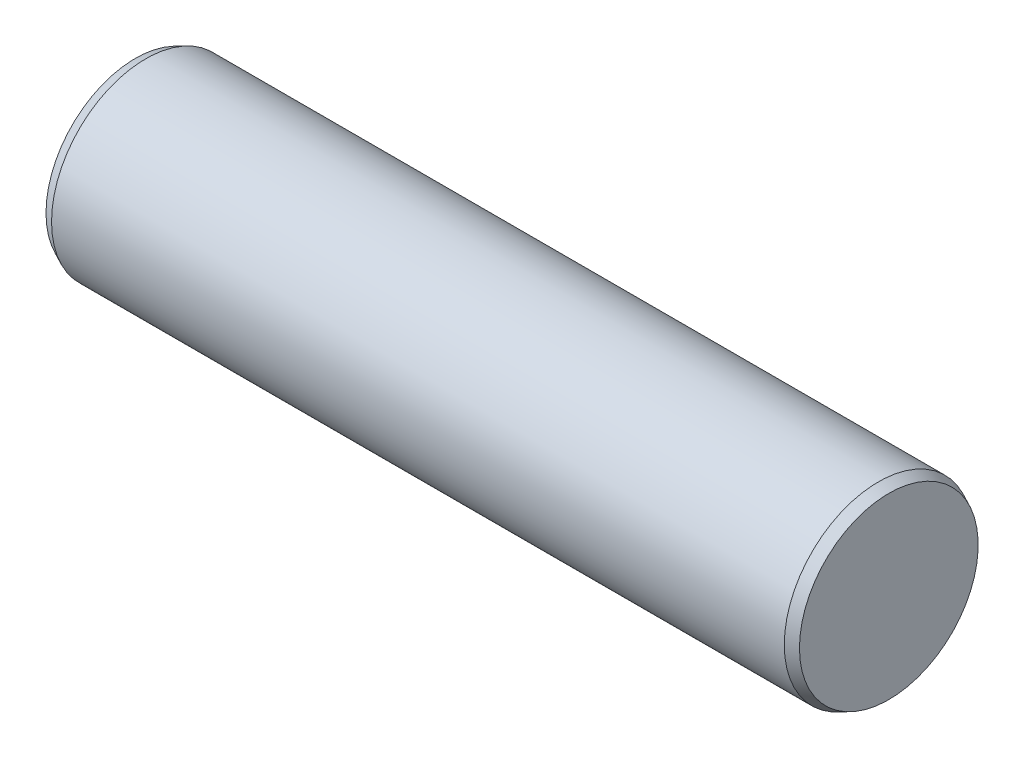
SolidWorks part; units mm, degrees
ref_plane "Plane1" through (0, 0, 0) normal (0, 0, 1) x (1, 0, 0)
ref_plane "Plane2" through (0, 0, 0) normal (0, 1, 0) x (1, 0, 0)
ref_plane "Plane3" through (0, 0, 0) normal (1, 0, 0) x (0, 0, -1)
sketch "Sketch1" plane through (0, 0, 0) normal (0, 0, 1) x (1, 0, 0)
  line L1 (-6.35, 0) -> (107.95, 0) construction
  line L2 (0, 0) -> (101.6, 0)
  line L3 (101.6, 0) -> (101.6, 12.0486)
  line L4 (101.6, 12.0486) -> (100.203, 12.7)
  line L5 (100.203, 12.7) -> (1.397, 12.7)
  line L6 (0, 12.0486) -> (0, 0)
  line L7 (1.397, 12.7) -> (0, 12.0486)
  dimension "D3" = 25
  dimension "Diameter" = 25.4
  dimension "D1" = 25
  dimension "D2" = 1.397
  dimension "Length" = 101.6
revolve "Base-Revolve" add sketch "Sketch1" angle 360 about L1
equation "\"D2@Sketch1\" = \"Chamfer_length@Sketch1\""
